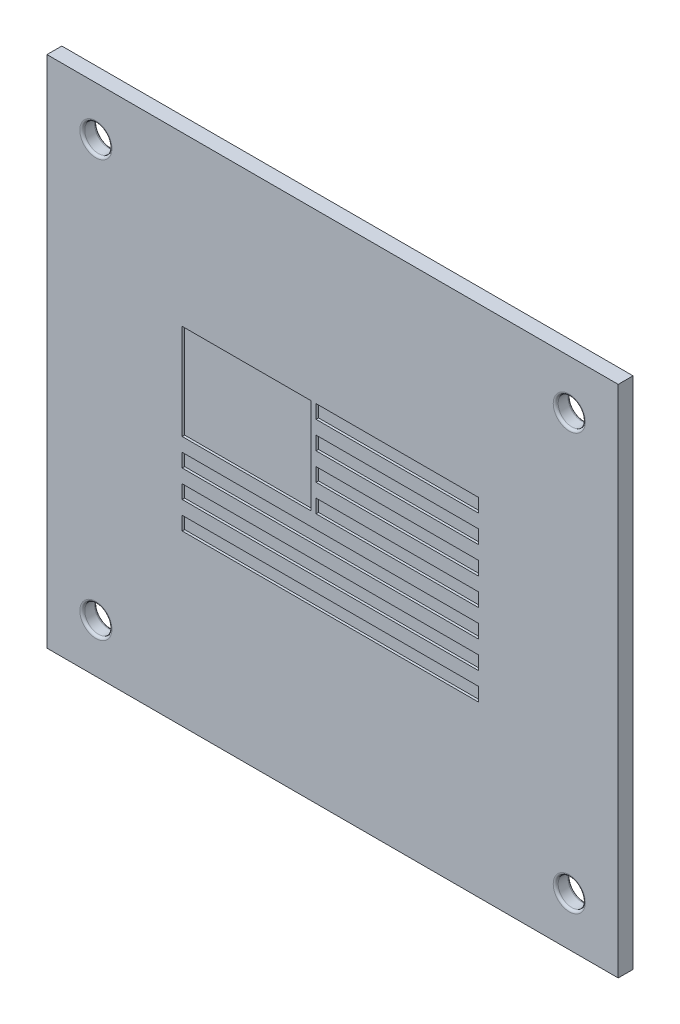
SolidWorks part; units mm, degrees
ref_plane "Front Plane" through (0, 0, 0) normal (0, 0, 1) x (1, 0, 0)
ref_plane "Top Plane" through (0, 0, 0) normal (0, 1, 0) x (1, 0, 0)
ref_plane "Right Plane" through (0, 0, 0) normal (1, 0, 0) x (0, 0, -1)
sketch "Sketch1" plane through (0, 0, 0) normal (0, 0, 1) x (1, 0, 0)
  line L1 (-57.8, -52.02) -> (57.8, -52.02)
  line L2 (-57.8, -52.02) -> (-57.8, 52.02)
  line L3 (-57.8, 52.02) -> (57.8, 52.02)
  line L4 (57.8, -52.02) -> (57.8, 52.02)
  line L5 (-57.8, -52.02) -> (57.8, 52.02) construction
  line L6 (-57.8, 52.02) -> (57.8, -52.02) construction
  point P0 (0, 0)
  dimension "D1" = 115.6
  dimension "D2" = 104.04
extrude "Boss-Extrude1" add sketch "Sketch1" along normal blind 3
sketch "Sketch2" plane through (0, 0, 3) normal (0, 0, 1) x (1, 0, 0)
  line L0 (57.8, 52.02) -> (-57.8, 52.02) construction
  line L1 (-57.8, 52.02) -> (-57.8, -52.02) construction
  line L2 (0, 0) -> (0, 50000) construction
  line L3 (0, 0) -> (50000, 0) construction
  circle A0 centre (-47.9, 42.12) radius 2.75
  circle A1 centre (47.9, 42.12) radius 2.75
  circle A2 centre (47.9, -42.12) radius 2.75
  circle A3 centre (-47.9, -42.12) radius 2.75
  dimension "D1" = 9.9
  dimension "D3" = 5.5
  dimension "D2" = 9.9
extrude "Cut-Extrude1" cut sketch "Sketch2" against normal through all
sketch "Sketch3" [suppressed] plane through (0, 0, 3) normal (0, 0, 1) x (1, 0, 0)
  text T1 "<b>  School of </b>\r\n<b>Engineering</b>\r\n<b>Technology</b>" font "Century Gothic" height in points 48
extrude "Cut-Extrude2" [suppressed] cut sketch "Sketch3" against normal blind 0.5
sketch "Sketch5" plane through (0, 0, 3) normal (0, 0, 1) x (1, 0, 0)
  line L0 (-9.7309, 10.0231) -> (-15.5666, -6.0101)
  line L1 (-15.5666, -6.0101) -> (-22.7346, -6.0101)
  line L2 (-22.7346, -6.0101) -> (-25.4708, -13.5277)
  line L3 (-25.4708, -13.5277) -> (-1.3321, -13.5277)
  line L4 (-1.3321, -13.5277) -> (1.4041, -6.0101)
  line L5 (1.4041, -6.0101) -> (-2.2976, -6.0101)
  line L6 (-2.2976, -6.0101) -> (-1.2716, -3.1911)
  line L7 (-1.2716, -3.1911) -> (15.0107, -3.1911)
  line L8 (-11.7357, 17.5407) -> (15.0107, 17.5407)
  line L9 (-16.899, 10.0231) -> (-9.7309, 10.0231)
  line L10 (-16.899, 10.0231) -> (-14.1628, 17.5407)
  line L11 (-14.1628, 17.5407) -> (-11.7357, 17.5407)
  line L12 (1.8173, 5.2954) -> (3.1853, 9.0542)
  line L13 (3.1853, 9.0542) -> (15.0107, 9.0542)
  line L14 (1.8173, 5.2954) -> (15.0107, 5.2954)
  line L15 (-12.5872, 8.0231) -> (-16.967, -4.0101)
  line L16 (-16.967, -4.0101) -> (-24.1351, -4.0101)
  line L17 (-24.1351, -4.0101) -> (-28.3271, -15.5277)
  line L18 (-28.3271, -15.5277) -> (0.0683, -15.5277)
  line L19 (-11.7357, 19.5407) -> (15.0107, 19.5407)
  line L20 (-15.5633, 19.5407) -> (-11.7357, 19.5407)
  line L21 (-19.7553, 8.0231) -> (-15.5633, 19.5407)
  line L22 (-19.7553, 8.0231) -> (-12.5872, 8.0231)
  line L24 (0.0683, -15.5277) -> (3.8305, -5.1911)
  line L26 (3.8305, -5.1911) -> (15.0107, -5.1911)
  arc A0 (15.0107, 17.5407) -> (15.0107, -3.1911) centre (15.0107, 7.1748) cw
  arc A1 (15.0107, 9.0542) -> (15.0107, 5.2954) centre (15.0107, 7.1748) cw
  arc A2 (15.0107, 19.5407) -> (15.0107, -5.1911) centre (15.0107, 7.1748) cw
  point P2 (2.5013, 7.1748)
  dimension "D1" = 3
  dimension "D2" = 4
extrude "Cut-Extrude4" [suppressed] cut sketch "Sketch5" against normal blind 0.5 contours A1 L13 L12 L14 | A2 L19 L20 L21 L22 L15 L16 L17 L18 L24 L26 L8 A0 L7 L6 L5 L4 L3 L2 L1 L0 L9 L10 L11
sketch "Sketch7" plane through (0, 0, 3) normal (0, 0, 1) x (1, 0, 0)
  line L6 (-30.4289, 18.0795) -> (-30.4289, -17.8005)
  line L9 (29.5711, 18.0795) -> (-30.4289, 18.0795)
  line L10 (29.7809, 15.3195) -> (-3.3534, 15.3195)
  line L12 (29.5711, 18.0795) -> (29.5711, -17.8005)
  line L13 (29.7809, 12.5595) -> (-3.3534, 12.5595)
  line L14 (29.7809, 9.7995) -> (-3.3534, 9.7995)
  line L16 (29.7809, 7.0395) -> (-3.3534, 7.0395)
  line L580 (29.7809, 4.2795) -> (-3.3534, 4.2795)
  line L581 (29.7809, 1.5195) -> (-3.3534, 1.5195)
  line L582 (29.5711, -1.2405) -> (-30.4289, -1.2405)
  line L584 (29.5711, -4.0005) -> (-30.4289, -4.0005)
  line L1148 (29.5711, -6.7605) -> (-30.4289, -6.7605)
  line L1149 (29.5711, -9.5205) -> (-30.4289, -9.5205)
  line L1150 (29.5711, -12.2805) -> (-30.4289, -12.2805)
  line L1151 (-30.4289, -1.2405) -> (-30.4289, 18.0795)
  line L1152 (29.5711, -15.0405) -> (-30.4289, -15.0405)
  line L1153 (29.5711, -17.8005) -> (-30.4289, -17.8005)
  line L1154 (-30.4289, -1.2405) -> (-4.3534, -1.2405)
  line L1155 (-4.3534, 1.5195) -> (-4.3534, 4.2795)
  line L1156 (-30.4289, 18.0795) -> (-4.3534, 18.0795)
  line L1729 (-4.3534, 12.5595) -> (-4.3534, 15.3195)
  line L1730 (-4.3534, 7.0395) -> (-4.3534, 9.7995)
  line L1731 (-4.3534, 18.0795) -> (-4.3534, -1.2405)
  line L1732 (-3.3534, 18.0795) -> (-3.3534, -1.2405)
  dimension "D1" = 1
extrude "Cut-Extrude7" cut sketch "Sketch7" against normal blind 0.5 contours L1731 L9 L6 L582 L1155 L1730 L1729 | L9 L1732 L10 L12 | L13 L1732 L14 L12 | L16 L1732 L580 L12 | L581 L1732 L582 L12 | L1148 L12 L584 L6 | L1150 L12 L1149 L6 | L1153 L12 L1152 L6 region at (-17.3911, 8.4195, 3) region at (-0.4289, -5.3805, 3) region at (13.1089, 16.6995, 3) region at (13.1089, 0.1395, 3) region at (-0.4289, -10.9005, 3) region at (13.1089, 11.1795, 3) region at (13.1089, 5.6595, 3) region at (-0.4289, -16.4205, 3)
sketch "Sketch8" [suppressed] plane through (0, 0, 3) normal (0, 0, 1) x (1, 0, 0)
  text T0 "<b>    Purdue</b>\r\n<b>Polytechnic</b>\r\n<b>    Institute</b>" font "Century Gothic" height in points 48
extrude "Cut-Extrude8" [suppressed] cut sketch "Sketch8" against normal blind 0.5
fillet "Fillet1" radius 0.5 8 edges at (45.15, 42.12, 3) (45.15, 42.12, 0) (50.65, -42.12, 3) (50.65, -42.12, 0) (-50.65, -42.12, 3) (-50.65, -42.12, 0) (-45.15, 42.12, 3) (-45.15, 42.12, 0)
